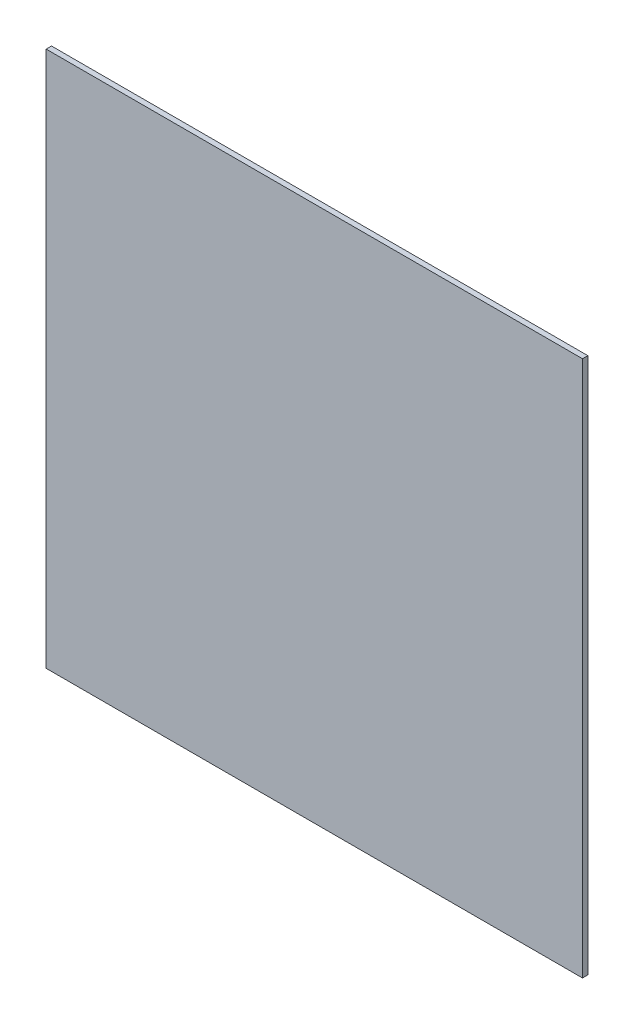
SolidWorks part; units mm, degrees
ref_plane "Front Plane" through (0, 0, 0) normal (0, 0, 1) x (1, 0, 0)
ref_plane "Top Plane" through (0, 0, 0) normal (0, 1, 0) x (1, 0, 0)
ref_plane "Right Plane" through (0, 0, 0) normal (1, 0, 0) x (0, 0, -1)
other "Configuration Table"
sketch "Sketch1" plane through (0, 0, 0) normal (0, 0, 1) x (1, 0, 0)
  line L1 (0, 0) -> (304.8, 0)
  line L2 (0, 0) -> (0, 304.8)
  line L3 (0, 304.8) -> (304.8, 304.8)
  line L4 (304.8, 0) -> (304.8, 304.8)
sheet metal parameters "Sheet-Metal1" thickness 3.048 parameters "D1"=0.7366
base flange "Base-Flange1" sketch "Sketch1" thickness 3.048 reverse thickness direction yes parameters "D1"=0.7366
flat pattern "Flat-Pattern1" [suppressed]
sketch "Bend-Lines1" plane through (0, 0, 0) normal (0, 1, 0) x (-1, 0, 0)
